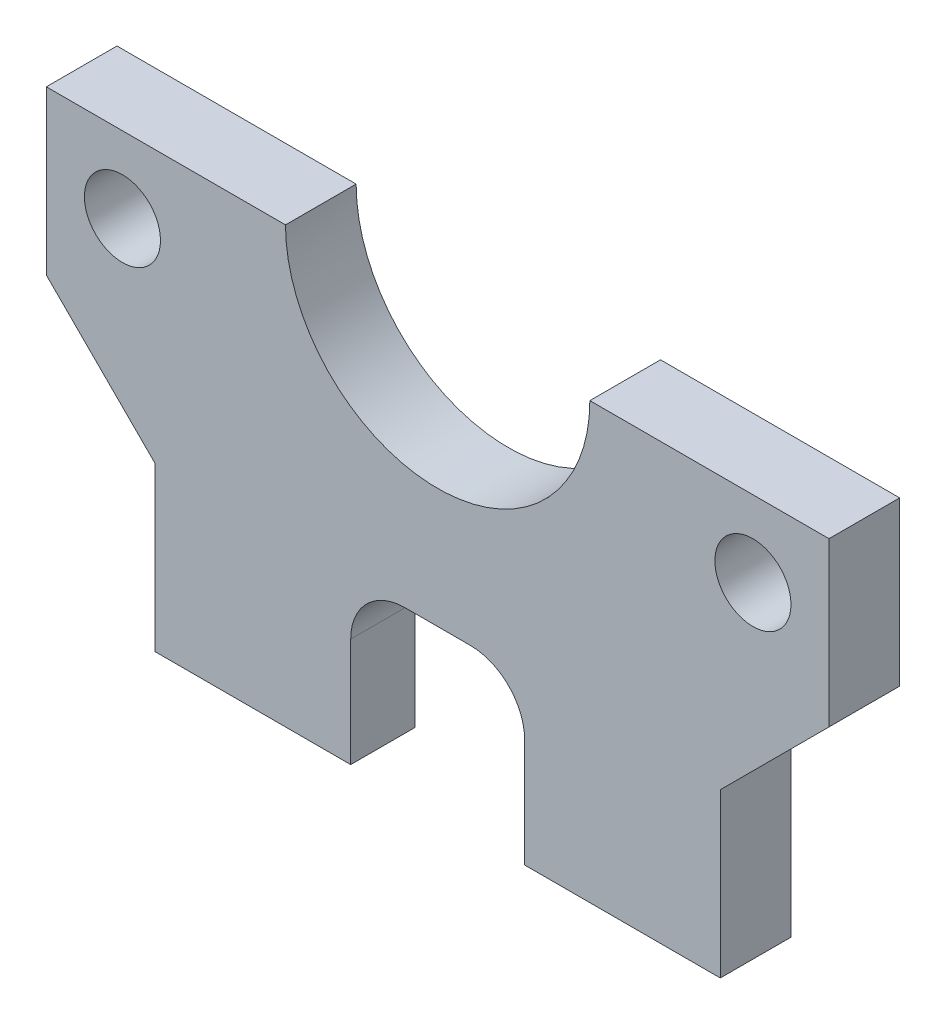
SolidWorks part; units mm, degrees
ref_plane "Front Plane" through (0, 0, 0) normal (0, 0, 1) x (1, 0, 0)
ref_plane "Top Plane" through (0, 0, 0) normal (0, 1, 0) x (1, 0, 0)
ref_plane "Right Plane" through (0, 0, 0) normal (1, 0, 0) x (0, 0, -1)
sketch "Sketch1" plane through (0, 0, 0) normal (0, 0, 1) x (1, 0, 0)
  line L1 (-26, -20) -> (26, -20)
  line L2 (-26, -20) -> (-26, 20)
  line L3 (-26, 20) -> (26, 20)
  line L4 (26, -20) -> (26, 20)
  line L5 (-26, -20) -> (26, 20) construction
  line L6 (-26, 20) -> (26, -20) construction
  point P0 (0, 0)
  dimension "D1" = 40
  dimension "D2" = 52
extrude "Boss-Extrude1" add sketch "Sketch1" along normal blind 6.5
sketch "Sketch10" plane through (0, 0, 0) normal (0, 0, -1) x (-1, 0, 0)
  line L1 (26, 20) -> (36, 20)
  line L2 (26, 20) -> (26, 5)
  line L3 (26, 5) -> (36, 5)
  line L4 (36, 20) -> (36, 5)
  line L5 (-26, 20) -> (-36, 20)
  line L6 (-26, 20) -> (-26, 5)
  line L7 (-26, 5) -> (-36, 5)
  line L8 (-36, 20) -> (-36, 5)
  dimension "D1" = 10
  dimension "D2" = 15
  dimension "D3" = 10
  dimension "D4" = 15
extrude "Boss-Extrude2" add sketch "Sketch10" against normal up to surface (6.5 mm away) up to face at (0, 0, 6.5)
chamfer "Chamfer1" distance 10 angle 45 2 edges at (26, 5, 3.25) (-26, 5, 3.25)
sketch "Sketch5" plane through (0, -20, 0) normal (0, -1, 0) x (1, 0, 0)
  line L3 (-26, 0) -> (26, 0)
  line L4 (-26, 0) -> (-26, 0.9258)
  line L5 (-26, 6.5) -> (-26, 0) construction
  line L6 (-26, 0.9258) -> (26, 0)
  dimension "D1" = 178.98
extrude "Cut-Extrude4" cut sketch "Sketch5" against normal blind 25
sketch "Sketch6" plane through (0, 0, 6.5) normal (0, 0, 1) x (1, 0, 0)
  line L0 (36, 20) -> (-36, 20) construction
  circle A0 centre (0, 20) radius 14
  dimension "D1" = 28
extrude "Cut-Extrude5" cut sketch "Sketch6" against normal blind 10
sketch "Sketch7" plane through (0, 0, 6.5) normal (0, 0, 1) x (1, 0, 0)
  line L0 (36, 20) -> (14, 20) construction
  line L1 (-14, 20) -> (-36, 20) construction
  line L4 (-26, 5) -> (-26, -5) construction
  line L5 (26, 5) -> (26, -5) construction
  circle A0 centre (29, 13) radius 3.5
  circle A1 centre (-29, 13) radius 3.5
  dimension "D1" = 7
  dimension "D2" = 7
  dimension "D4" = 3
  dimension "D5" = 7
  dimension "D6" = 7
  dimension "D3" = 3
extrude "Cut-Extrude6" cut sketch "Sketch7" against normal blind 10
sketch "Sketch8" plane through (0, -20, 0) normal (0, -1, 0) x (1, 0, 0)
  line L0 (26, 6.5) -> (26, 0) construction
  line L1 (-26, 6.5) -> (26, 6.5) construction
  text T0 "Right"
  dimension "D1" = 13
  dimension "D2" = 4.5
extrude "Cut-Extrude7" cut sketch "Sketch8" against normal blind 1
sketch "Sketch9" plane through (0, 0, 6.5) normal (0, 0, 1) x (1, 0, 0)
  line L0 (-26, -20) -> (26, -20) construction
  line L1 (8, -20) -> (-8, -20)
  line L2 (8, -20) -> (8, -5)
  line L3 (8, -5) -> (-8, -5)
  line L4 (-8, -20) -> (-8, -5)
  line L5 (26, -20) -> (26, -5) construction
  point P6 (0, -20)
  point P7 (0, -20)
  dimension "D1" = 18
  dimension "D2" = 15
extrude "Cut-Extrude8" cut sketch "Sketch9" against normal blind 10
fillet "Fillet1" radius 5 2 edges at (8, -5, 3.4102) (-8, -5, 3.5527)
sketch "Sketch11" plane through (0, -20, 0) normal (0, -1, 0) x (1, 0, 0)
  line L0 (-26, 0.9258) -> (-36, 1.1039)
  line L1 (-36, 6.5) -> (-36, 0) construction
  line L2 (-36, 1.1039) -> (-36, 0)
  line L3 (-36, 0) -> (-26, 0)
  line L4 (-26, 0) -> (-26, 0.9258)
  line L5 (26, 0) -> (-26, 0.9258) construction
extrude "Cut-Extrude9" cut sketch "Sketch11" against normal blind 25
